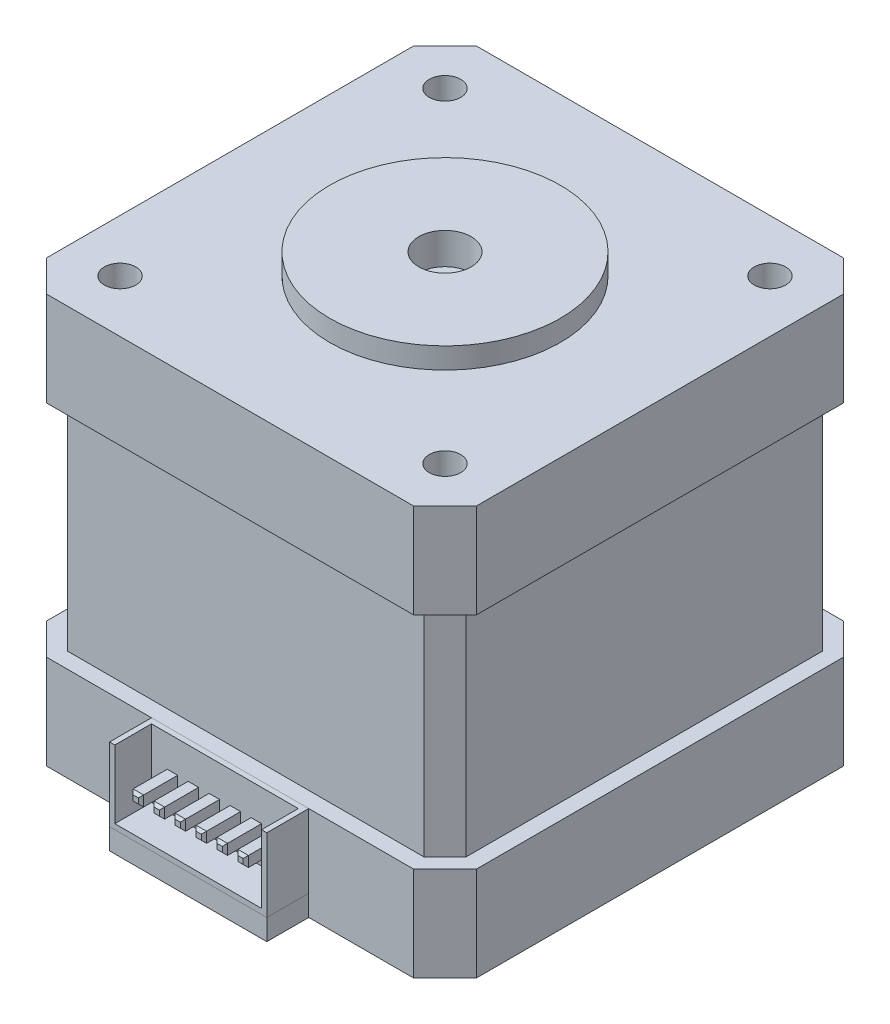
SolidWorks part; units mm, degrees
ref_plane "Front Plane" through (0, 0, 0) normal (0, 0, 1) x (1, 0, 0)
ref_plane "Top Plane" through (0, 0, 0) normal (0, 1, 0) x (1, 0, 0)
ref_plane "Right Plane" through (0, 0, 0) normal (1, 0, 0) x (0, 0, -1)
sketch "Sketch2" plane through (0, 0, 0) normal (0, 1, 0) x (1, 0, 0)
  line L1 (-20.5, -20.5) -> (20.5, -20.5)
  line L2 (-20.5, -20.5) -> (-20.5, 20.5)
  line L3 (-20.5, 20.5) -> (20.5, 20.5)
  line L4 (20.5, -20.5) -> (20.5, 20.5)
  line L5 (-20.5, -20.5) -> (20.5, 20.5) construction
  line L6 (-20.5, 20.5) -> (20.5, -20.5) construction
  point P0 (0, 0)
  dimension "D1" = 41
extrude "Boss-Extrude1" add sketch "Sketch2" along normal blind 39 contours L2 L3 L4 L1
chamfer "Chamfer1" distance 3 angle 45 4 edges at (20.5, 19.5, 20.5) (-20.5, 19.5, 20.5) (-20.5, 19.5, -20.5) (20.5, 19.5, -20.5)
sketch "Sketch3" plane through (0, 39, 0) normal (0, 1, 0) x (1, 0, 0)
  line L0 (-19, -19) -> (19, 19) construction
  line L1 (-20.5, -17.5) -> (-17.5, -20.5) construction
  line L2 (20.5, 17.5) -> (17.5, 20.5) construction
  line L3 (-19, 19) -> (19, -19) construction
  line L4 (-17.5, 20.5) -> (-20.5, 17.5) construction
  line L5 (17.5, -20.5) -> (20.5, -17.5) construction
  line L6 (0, 0) -> (0, 20.5) construction
  line L7 (-17.5, 20.5) -> (17.5, 20.5) construction
  circle A0 centre (-15.5, -15.5) radius 1.5
  circle A1 centre (15.5, -15.5) radius 1.5
  circle A2 centre (-15.5, 15.5) radius 1.5
  circle A3 centre (15.5, 15.5) radius 1.5
  dimension "D1" = 3
  dimension "D2" = 31
  dimension "D4" = 31
  dimension "D3" = 2
extrude "Cut-Extrude1" cut sketch "Sketch3" against normal blind 4
ref_plane "Plane1" through (0, 19.5, 0) normal (0, -1, 0) x (-1, 0, 0)
mirror "Mirror1" about plane through (0, 19.5, 0) normal (0, -1, 0) of "Cut-Extrude1"
sketch "Sketch4" plane through (0, 39, 0) normal (0, 1, 0) x (1, 0, 0)
  circle A0 centre (0, 0) radius 11
  dimension "D1" = 22
extrude "Boss-Extrude2" add sketch "Sketch4" along normal blind 2
sketch "Sketch5" plane through (0, 41, 0) normal (0, 1, 0) x (1, 0, 0)
  circle A0 centre (0, 0) radius 2.5
  dimension "D1" = 5
sketch "Sketch7" plane through (0, 0, 0) normal (0, -1, 0) x (1, 0, 0)
  line L0 (-17.5, 20.5) -> (17.5, 20.5) construction
  line L1 (-19, -19) -> (19, -19)
  line L2 (-19, -19) -> (-19, 19)
  line L3 (-19, 19) -> (19, 19)
  line L4 (19, -19) -> (19, 19)
  line L5 (-19, -19) -> (19, 19) construction
  line L6 (-19, 19) -> (19, -19) construction
  line L7 (20.5, 17.5) -> (20.5, -17.5) construction
  point P0 (0, 0)
  dimension "D1" = 1.5
  dimension "D2" = 1.5
extrude "Cut-Extrude3" cut sketch "Sketch7" against normal blind 21 from offset 9 flip side to cut offset against normal yes
chamfer "Chamfer5" distance 2 angle 45 4 edges at (-19, 19.5, 19) (-19, 19.5, -19) (19, 19.5, -19) (19, 19.5, 19)
sketch "Sketch8" plane through (0, 0, 20.5) normal (0, 0, 1) x (1, 0, 0)
  line L0 (0, 2) -> (0, 9) construction
  line L1 (-17.5, 0) -> (17.5, 0) construction
  line L2 (17, 9) -> (-17, 9) construction
  line L3 (-7.5, 0) -> (7.5, 0)
  line L4 (-7.5, 0) -> (-7.5, 2)
  line L5 (-7.5, 2) -> (7.5, 2)
  line L6 (7.5, 0) -> (7.5, 2)
  line L7 (-7, 2.5) -> (-7, 8.5)
  line L8 (-7.5, 2) -> (7.5, 2)
  line L9 (-7.5, 2) -> (-7.5, 9)
  line L10 (-7.5, 9) -> (7.5, 9)
  line L11 (7.5, 2) -> (7.5, 9)
  line L12 (-7.5, 2) -> (7.5, 9) construction
  line L13 (-7.5, 9) -> (7.5, 2) construction
  line L14 (-7, 8.5) -> (7, 8.5) construction
  line L15 (7, 2.5) -> (7, 8.5)
  line L16 (-7, 2.5) -> (7, 2.5)
  line L17 (7, 8.5) -> (7, 9)
  line L18 (-7, 8.5) -> (-7, 9)
  line L19 (0, 5.5) -> (7, 5.5) construction
  line L20 (2.5, 5) -> (2.5, 6)
  line L21 (4.5, 5) -> (5.5, 5)
  line L22 (4.5, 5) -> (4.5, 6)
  line L23 (4.5, 6) -> (5.5, 6)
  line L24 (5.5, 5) -> (5.5, 6)
  line L25 (4.5, 5) -> (5.5, 6) construction
  line L26 (4.5, 6) -> (5.5, 5) construction
  line L27 (2.5, 5) -> (3.5, 5)
  line L28 (3.5, 5) -> (3.5, 6)
  line L29 (2.5, 6) -> (3.5, 6)
  line L30 (0.5, 5) -> (0.5, 6)
  line L31 (0.5, 5) -> (1.5, 5)
  line L32 (1.5, 5) -> (1.5, 6)
  line L33 (0.5, 6) -> (1.5, 6)
  line L34 (-1.5, 5) -> (-1.5, 6)
  line L35 (-1.5, 5) -> (-0.5, 5)
  line L36 (-0.5, 5) -> (-0.5, 6)
  line L37 (-1.5, 6) -> (-0.5, 6)
  line L38 (-3.5, 5) -> (-3.5, 6)
  line L39 (-3.5, 5) -> (-2.5, 5)
  line L40 (-2.5, 5) -> (-2.5, 6)
  line L41 (-3.5, 6) -> (-2.5, 6)
  line L42 (-5.5, 5) -> (-5.5, 6)
  line L43 (-5.5, 5) -> (-4.5, 5)
  line L44 (-4.5, 5) -> (-4.5, 6)
  line L45 (-5.5, 6) -> (-4.5, 6)
  point P0 (0, 5.5)
  point P10 (0, 0)
  point P26 (5, 5.5)
  line M4 (17.5, 9) -> (-17.5, 9)
  dimension "D2" = 2
  dimension "D5" = 1
  dimension "D1" = 15
  dimension "D4" = 1
  dimension "D6" = 2
  dimension "D8" = 1.5
  dimension "D3" = 0.5
  dimension "D7" = 6
extrude "Cut-Extrude4" cut sketch "Sketch5" against normal blind 3
extrude "Boss-Extrude3" add sketch "Sketch8" along normal blind 4 contours L4 L3 L6 L5
extrude "Boss-Extrude4" add sketch "Sketch8<4>" along normal blind 0.5 separate body contours L18 L7 L16 L15 L17 L10 L24 L21 L22 L23 L20 L29 L28 L27 L30 L33 L32 L31 L34 L37 L36 L35 L38 L41 L40 L39 L42 L45 L44 L43 | L7 L18 L9 L5 L11 L17 L15 L16 M4 region at (-7.3345, 5.5, 20.5) region at (0, 5.7676, 20.5)
sketch "Sketch8<4>" plane through (0, 0, 20.5) normal (0, 0, 1) x (1, 0, 0) same geometry as "Sketch8"
extrude "Boss-Extrude5" add sketch "Sketch8<5>" along normal blind 4 separate body contours L7 L18 L9 L5 L11 L17 L15 L16 M4 region at (-7.3345, 5.5, 20.5)
sketch "Sketch8<5>" plane through (0, 0, 20.5) normal (0, 0, 1) x (1, 0, 0) same geometry as "Sketch8"
extrude "Boss-Extrude6" add sketch "Sketch8<6>" along normal blind 4 contours L21 L24 L23 L22 | L29 L20 L27 L28 | L33 L30 L31 L32 | L37 L34 L35 L36 | L41 L38 L39 L40 | L45 L42 L43 L44 region at (3, 5.5, 20.5) region at (5, 5.5, 20.5) region at (1, 5.5, 20.5) region at (-1, 5.5, 20.5) region at (-3, 5.5, 20.5) region at (-5, 5.5, 20.5)
sketch "Sketch8<6>" plane through (0, 0, 20.5) normal (0, 0, 1) x (1, 0, 0) same geometry as "Sketch8"
combine bodies "Combine1" operation type add bodies to combine 118 119
chamfer "Chamfer6" distance 0.25 angle 45 24 edges at (4.5, 5.5, 24.5) (5, 6, 24.5) (5.5, 5.5, 24.5) (5, 5, 24.5) (3.5, 5.5, 24.5) (3, 5, 24.5) (2.5, 5.5, 24.5) (3, 6, 24.5) (1.5, 5.5, 24.5) (1, 5, 24.5) (0.5, 5.5, 24.5) (1, 6, 24.5) (-0.5, 5.5, 24.5) (-1, 5, 24.5) (-1.5, 5.5, 24.5) (-1, 6, 24.5) (-2.5, 5.5, 24.5) (-3, 5, 24.5) (-3.5, 5.5, 24.5) (-3, 6, 24.5) (-4.5, 5.5, 24.5) (-5, 5, 24.5) (-5.5, 5.5, 24.5) (-5, 6, 24.5)
